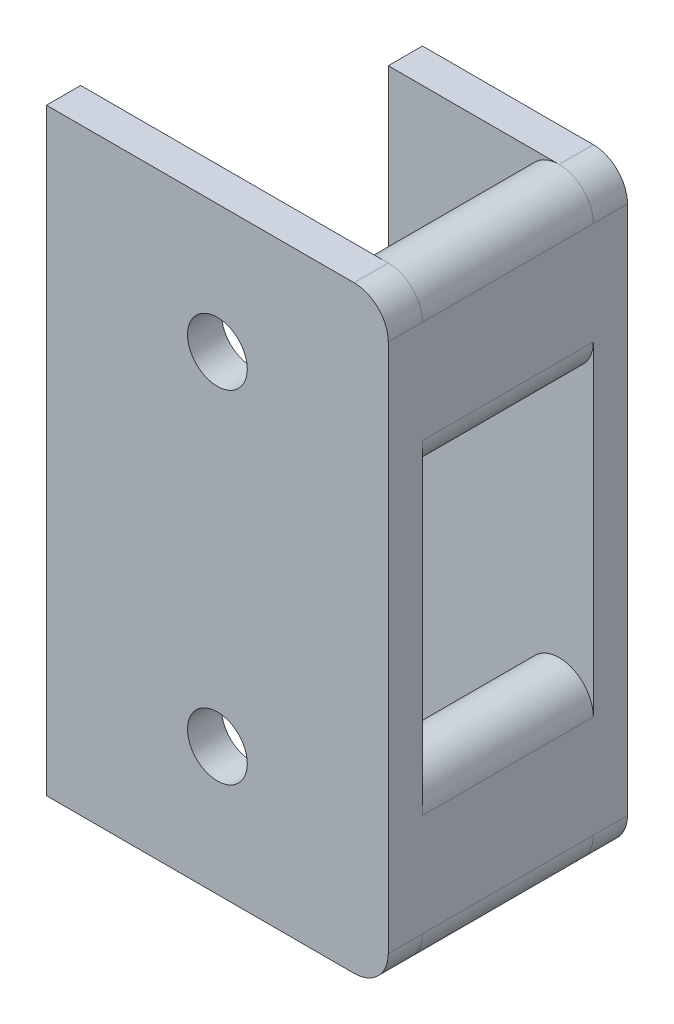
SolidWorks part; units mm, degrees
ref_plane "Plan de face" through (0, 0, 0) normal (0, 0, 1) x (1, 0, 0)
ref_plane "Plan de dessus" through (0, 0, 0) normal (0, 1, 0) x (1, 0, 0)
ref_plane "Plan de droite" through (0, 0, 0) normal (1, 0, 0) x (0, 0, -1)
sketch "Esquisse1" plane through (0, 0, 0) normal (0, 0, 1) x (1, 0, 0)
  line L0 (-6.6025, 20.2958) -> (3.3975, 20.2958) construction
  line L1 (3.3975, 2.7958) -> (-16.6025, 2.7958)
  line L2 (3.3975, 2.7958) -> (3.3975, 37.7958)
  line L3 (3.3975, 37.7958) -> (-16.6025, 37.7958)
  line L4 (-16.6025, 2.7958) -> (-16.6025, 37.7958)
  line L8 (-6.6025, 30.2958) -> (-6.6025, 10.2958) construction
  circle A1 centre (-6.6025, 30.2958) radius 1.75
  circle A2 centre (-6.6025, 10.2958) radius 1.75
  dimension "D2" = 3.5
  dimension "D1" = 20
  dimension "D3" = 10
  dimension "D4" = 20
  dimension "D5" = 35
extrude "Boss.-Extru.1" add sketch "Esquisse1" against normal blind 2
sketch "Esquisse2" plane through (0, 0, -2) normal (0, 0, -1) x (-1, 0, 0)
  line L0 (-1.3975, 35.7958) -> (-1.3975, 29.7958) construction
  line L1 (0.6025, 35.7958) -> (0.6025, 29.7958)
  line L2 (-3.3975, 35.7958) -> (-3.3975, 29.7958)
  line L3 (-3.3975, 2.7958) -> (-3.3975, 37.7958) construction
  line L4 (-3.3975, 20.2958) -> (16.6025, 20.2958) construction
  line L5 (16.6025, 37.7958) -> (16.6025, 2.7958) construction
  line L6 (-1.3975, 4.7958) -> (-1.3975, 10.7958) construction
  line L7 (0.6025, 4.7958) -> (0.6025, 10.7958)
  line L8 (-3.3975, 4.7958) -> (-3.3975, 10.7958)
  arc A0 (0.6025, 35.7958) -> (-3.3975, 35.7958) centre (-1.3975, 35.7958) ccw
  arc A1 (-3.3975, 29.7958) -> (0.6025, 29.7958) centre (-1.3975, 29.7958) ccw
  arc A2 (0.6025, 4.7958) -> (-3.3975, 4.7958) centre (-1.3975, 4.7958) cw
  arc A3 (-3.3975, 10.7958) -> (0.6025, 10.7958) centre (-1.3975, 10.7958) cw
  point P2 (-1.3975, 32.7958)
  point P15 (-1.3975, 7.7958)
  point P20 (-1.3975, 32.7723)
  dimension "D1" = 2
  dimension "D2" = 6
  dimension "D3" = 12.5
extrude "Boss.-Extru.2" add sketch "Esquisse2" along normal blind 10
sketch "Esquisse3" plane through (0, 0, -12) normal (0, 0, -1) x (-1, 0, 0)
  line L1 (-3.3975, 37.7958) -> (8.6025, 37.7958)
  line L2 (-3.3975, 37.7958) -> (-3.3975, 2.7958)
  line L3 (-3.3975, 2.7958) -> (8.6025, 2.7958)
  line L4 (8.6025, 37.7958) -> (8.6025, 2.7958)
  line L5 (16.6025, 2.7958) -> (-1.3975, 2.7958) construction
  point P5 (5.2839, 3.639)
  dimension "D1" = 12
extrude "Boss.-Extru.3" add sketch "Esquisse3" along normal blind 2
fillet "Congé1" radius 2 4 edges at (3.3975, 2.7958, -1) (3.3975, 37.7958, -13) (3.3975, 2.7958, -13) (3.3975, 37.7958, -1)
